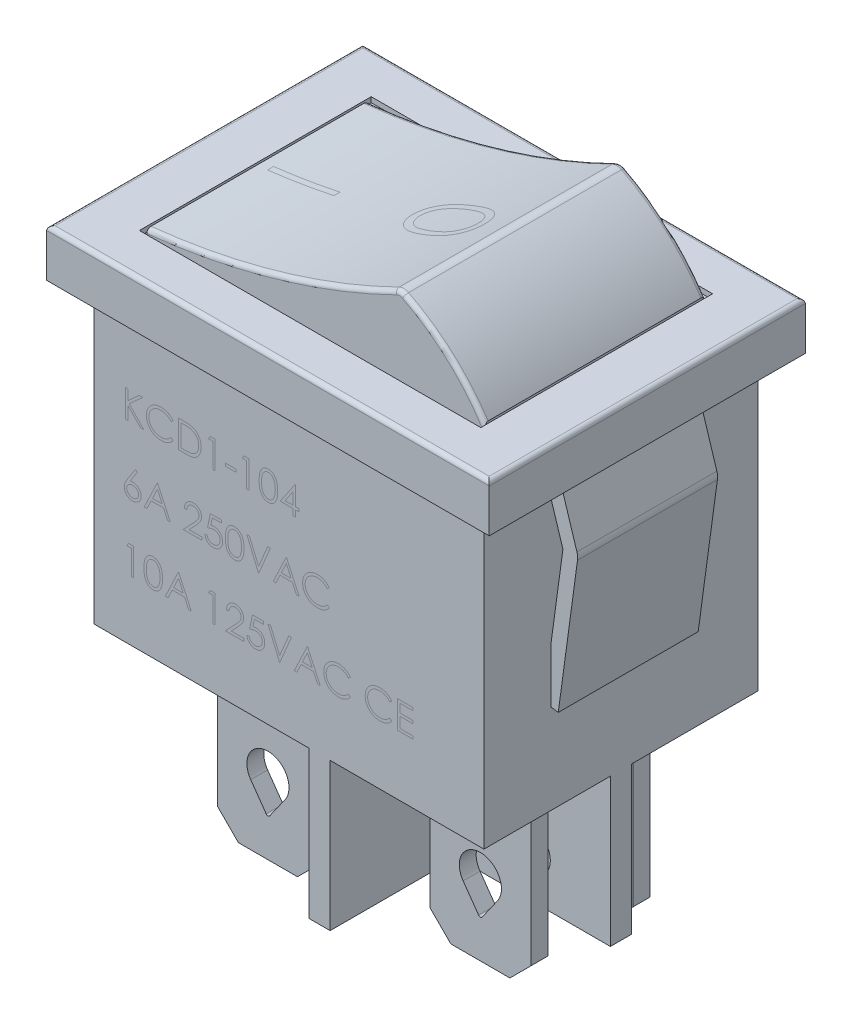
SolidWorks part; units mm, degrees
ref_plane "Front Plane" through (0, 0, 0) normal (0, 0, 1) x (1, 0, 0)
ref_plane "Top Plane" through (0, 0, 0) normal (0, 1, 0) x (1, 0, 0)
ref_plane "Right Plane" through (0, 0, 0) normal (1, 0, 0) x (0, 0, -1)
sketch "Sketch1" plane through (0, 0, 0) normal (0, 0, 1) x (1, 0, 0)
  line L1 (9.25, 7) -> (-9.25, 7)
  line L2 (9.25, 7) -> (9.25, -7)
  line L3 (9.25, -7) -> (-9.25, -7)
  line L4 (-9.25, 7) -> (-9.25, -7)
  line L5 (9.25, 7) -> (-9.25, -7) construction
  line L6 (9.25, -7) -> (-9.25, 7) construction
  point P0 (0, 0)
  dimension "D1" = 14
  dimension "D2" = 18.5
extrude "Boss-Extrude1" add sketch "Sketch1" along normal mid plane 13
sketch "Sketch2" plane through (0, 7, 0) normal (0, 1, 0) x (1, 0, 0)
  line L1 (10.5, 7.5) -> (-10.5, 7.5)
  line L2 (10.5, 7.5) -> (10.5, -7.5)
  line L3 (10.5, -7.5) -> (-10.5, -7.5)
  line L4 (-10.5, 7.5) -> (-10.5, -7.5)
  line L5 (10.5, 7.5) -> (-10.5, -7.5) construction
  line L6 (10.5, -7.5) -> (-10.5, 7.5) construction
  point P0 (0, 0)
  dimension "D1" = 15
  dimension "D2" = 21
extrude "Boss-Extrude2" add sketch "Sketch2" along normal blind 2.25
sketch "Sketch11" plane through (0, 9.25, 0) normal (0, 1, 0) x (1, 0, 0)
  line L1 (-8.1, -5.5) -> (8.1, -5.5)
  line L2 (-8.1, -5.5) -> (-8.1, 5.5)
  line L3 (-8.1, 5.5) -> (8.1, 5.5)
  line L4 (8.1, -5.5) -> (8.1, 5.5)
  line L5 (-8.1, -5.5) -> (8.1, 5.5) construction
  line L6 (-8.1, 5.5) -> (8.1, -5.5) construction
  line L7 (-10.5, 7.5) -> (-10.5, -7.5) construction
  point P0 (0, 0)
  dimension "D1" = 2.4
  dimension "D2" = 11
extrude "Cut-Extrude6" cut sketch "Sketch11" against normal blind 0.25
sketch "Sketch3" plane through (0, 0, 0) normal (0, 0, 1) x (1, 0, 0)
  line L0 (8, 9.25) -> (4, 12.75) construction
  line L1 (-8, 9.25) -> (-8.1, 9.25) construction
  line L2 (10.5, 9.25) -> (10.5, 7) construction
  line L4 (-10.5, 9.25) -> (-10.5, 7) construction
  line L5 (-8, 9.25) -> (8, 9.25) construction
  line L6 (-8, 9.25) -> (8, 9.25) construction
  line L7 (-8, 9.25) -> (-8, 8.95)
  line L8 (-8, 8.95) -> (8, 8.95)
  line L9 (8, 9.25) -> (8, 8.95)
  arc A0 (-8, 9.25) -> (3.779, 12.6405) centre (-11.6425, 44.0599) ccw
  arc A1 (4.2281, 12.6363) -> (8, 9.25) centre (-0.3483, 3.7449) cw
  arc A2 (3.779, 12.6405) -> (4.2281, 12.6363) centre (3.9993, 12.1917) cw
  point P6 (-8, 9.25)
  dimension "D4" = 35
  dimension "D5" = 6.5
  dimension "D6" = 10
  dimension "D7" = 0.5
  dimension "D1" = 2.5
  dimension "D2" = 3.5
  dimension "D3" = 2.5
  dimension "D8" = 0.3
extrude "Boss-Extrude3" add sketch "Sketch3" along normal mid plane 10.5
sketch "Sketch4" plane through (0, -7, 0) normal (0, -1, 0) x (-1, 0, 0)
  line L0 (-9.25, 6.5) -> (9.25, 6.5) construction
  line L1 (-1.95, 6.5) -> (-0.95, 6.5)
  line L2 (-1.95, 6.5) -> (-1.95, -6.5)
  line L3 (-1.95, -6.5) -> (-0.95, -6.5)
  line L4 (-0.95, 6.5) -> (-0.95, -6.5)
  line L5 (9.25, -6.5) -> (-9.25, -6.5) construction
  line L6 (-9.25, -6.5) -> (-9.25, 6.5) construction
  line L7 (-1.45, -6.5) -> (-1.45, 6.5) construction
  line L8 (-9.25, 0.5) -> (9.25, 0.5)
  line L9 (-9.25, 0.5) -> (-9.25, -0.5)
  line L10 (-9.25, -0.5) -> (9.25, -0.5)
  line L11 (9.25, 0.5) -> (9.25, -0.5)
  line L12 (-9.25, 0.5) -> (9.25, -0.5) construction
  line L13 (-9.25, -0.5) -> (9.25, 0.5) construction
  line L14 (9.25, -6.5) -> (9.25, 6.5) construction
  line L15 (0, 0) -> (4.2269, 0) construction
  line M5 (9.25, 6.5) -> (-9.25, 6.5)
  line M6 (-9.25, 6.5) -> (-9.25, -6.5)
  line M7 (-9.25, -6.5) -> (9.25, -6.5)
  line M8 (9.25, -6.5) -> (9.25, 6.5)
  dimension "D1" = 8.3
  dimension "D2" = 1
extrude "Boss-Extrude4" add sketch "Sketch4" along normal blind 7 contours L10 L2 L8 M6 | L4 L10 L8 M8 | L2 L10 L4 L8 | L2 L8 L4 M5 | L10 L2 L4 M7 region at (1.45, -7, -3.5) region at (1.45, -7, 0) region at (5.6, -7, 0) region at (-4.15, -7, 0) region at (1.45, -7, 3.5)
sketch "Sketch5" plane through (0, -7, 0) normal (0, -1, 0) x (1, 0, 0)
  line L0 (1.95, 6.5) -> (9.25, 6.5) construction
  line L1 (3, 2.82) -> (7.8, 2.82)
  line L2 (3, 2.82) -> (3, 2.02)
  line L3 (3, 2.02) -> (7.8, 2.02)
  line L4 (7.8, 2.82) -> (7.8, 2.02)
  line L5 (3, 2.82) -> (7.8, 2.02) construction
  line L6 (3, 2.02) -> (7.8, 2.82) construction
  line L7 (-6.2, -2.9) -> (-1.4, -2.9)
  line L8 (-6.2, -2.9) -> (-6.2, -3.7)
  line L9 (-6.2, -3.7) -> (-1.4, -3.7)
  line L10 (-1.4, -2.9) -> (-1.4, -3.7)
  line L11 (-6.2, -2.9) -> (-1.4, -3.7) construction
  line L12 (-6.2, -3.7) -> (-1.4, -2.9) construction
  line L13 (-9.25, -6.5) -> (0.95, -6.5) construction
  line L14 (9.25, 6.5) -> (9.25, -6.5) construction
  line L15 (0, 0) -> (-13.591, 0) construction
  line L16 (0, 0) -> (0, 9.8331) construction
  line L17 (3, -2.02) -> (7.8, -2.82) construction
  line L18 (3, -2.82) -> (7.8, -2.02) construction
  line L19 (7.8, -2.82) -> (7.8, -2.02)
  line L20 (3, -2.02) -> (7.8, -2.02)
  line L21 (3, -2.82) -> (3, -2.02)
  line L22 (3, -2.82) -> (7.8, -2.82)
  line L23 (-6.2, 3.7) -> (-1.4, 2.9) construction
  line L24 (-6.2, 2.9) -> (-1.4, 3.7) construction
  line L25 (-1.4, 2.9) -> (-1.4, 3.7)
  line L26 (-6.2, 3.7) -> (-1.4, 3.7)
  line L27 (-6.2, 2.9) -> (-6.2, 3.7)
  line L28 (-6.2, 2.9) -> (-1.4, 2.9)
  point P0 (5.4, 2.42)
  point P5 (-3.8, -3.3)
  point P24 (5.4, -2.42)
  point P29 (-3.8, 3.3)
  dimension "D1" = 4.8
  dimension "D2" = 0.8
  dimension "D3" = 14
  dimension "D4" = 3.68
  dimension "D5" = 2.8
  dimension "D6" = 1.45
extrude "Boss-Extrude5" add sketch "Sketch5" along normal blind 8.36
chamfer "Chamfer2" distance 1 angle 45 8 edges at (7.8, -15.36, 2.42) (3, -15.36, 2.42) (-1.4, -15.36, -3.3) (-6.2, -15.36, -3.3) (7.8, -15.36, -2.42) (3, -15.36, -2.42) (-1.4, -15.36, 3.3) (-6.2, -15.36, 3.3)
sketch "Sketch6" plane through (0, 0, 2.82) normal (0, 0, 1) x (1, 0, 0)
  line L0 (6.8, -15.36) -> (4, -15.36) construction
  line L1 (5.3183, -13.5177) -> (4.5832, -12.4769)
  line L2 (5.4, -11.9) -> (5.4, -15.36) construction
  line L3 (-1.4, -10.68) -> (3, -10.68) construction
  line L4 (5.4817, -13.5177) -> (6.2168, -12.4769)
  line L5 (-1.4, -14.36) -> (-1.4, -7) construction
  line L6 (3, -14.36) -> (3, -7) construction
  line L7 (0.8, -10.68) -> (0.8, -14.52) construction
  line L9 (-3.8817, -13.5177) -> (-4.6168, -12.4769)
  line L10 (-3.7183, -13.5177) -> (-2.9832, -12.4769)
  arc A0 (6.2168, -12.4769) -> (4.5832, -12.4769) centre (5.4, -11.9) ccw
  arc A1 (5.4817, -13.5177) -> (5.3183, -13.5177) centre (5.4, -13.46) cw
  arc A2 (-3.8817, -13.5177) -> (-3.7183, -13.5177) centre (-3.8, -13.46) ccw
  arc A3 (-4.6168, -12.4769) -> (-2.9832, -12.4769) centre (-3.8, -11.9) cw
  dimension "D1" = 0.1
  dimension "D2" = 2.66
  dimension "D3" = 1
  dimension "D4" = 1.8
extrude "Cut-Extrude1" cut sketch "Sketch6" against normal through all and the other way through all
ref_plane "Plane2" through (-3.071, 10.6688, 0) normal (0.2766, -0.961, 0) x (-0.961, -0.2766, 0)
sketch "Sketch7" plane through (-3.071, 10.6688, 0) normal (0.2766, -0.961, 0) x (-0.961, -0.2766, 0)
  text T0 "<r90>I</r>" font "Century Gothic" height 3.2
  text T1 "<r90>0</r>"
wrap "Wrap1" sketch "Sketch7" wrap type scribe source sketch "Sketch7" face at (-2.0357, 10.6854, 0)
sketch "Sketch8" plane through (0, 0, 6.5) normal (0, 0, 1) x (1, 0, 0)
  text T0 "KCD1-104\r\n6A 250VAC\r\n10A 125VAC CE" font "Century Gothic" height 1.3
wrap "Wrap2" sketch "Sketch8" wrap type scribe source sketch "Sketch8" face at (-0.3688, -6.125, 6.5)
sketch "Sketch9" plane through (0, 0, 0) normal (0, 0, 1) x (1, 0, 0)
  line L0 (-9.25, 7) -> (-10.175, 4.05)
  line L1 (-10.175, 4.05) -> (-9.25, -2.75)
  line L2 (-9.25, 7) -> (-9.25, -7) construction
  line L3 (9.25, 7) -> (10.175, 4.05)
  line L4 (10.175, 4.05) -> (9.25, -2.75)
  line L5 (9.25, -7) -> (9.25, 7) construction
  line L6 (-10.5, 7) -> (10.5, 7) construction
  dimension "D1" = 2.95
  dimension "D2" = 6.8
  dimension "D3" = 20.35
extrude "Extrude-Thin14" add sketch "Sketch9" against normal mid plane 6.64 separate body thin thin type mid plane wall 0.7
sketch "Sketch10" plane through (0, 0, 3.32) normal (0, 0, 1) x (1, 0, 0)
  line L2 (-9.25, -7) -> (9.25, -7)
  line L3 (-9.25, -7) -> (-9.25, 7)
  line L4 (-9.25, 7) -> (9.25, 7)
  line L5 (9.25, -7) -> (9.25, 7)
extrude "Cut-Extrude5" cut sketch "Sketch10" against normal through all
ref_axis "Ось1" through (0, -20.2999, 0) along (0, 1, 0)
fillet "Скругление1" radius 0.2 4 edges at (10.5, 9.25, 0) (0, 9.25, 7.5) (-10.5, 9.25, 0) (0, 9.25, -7.5)
fillet "Скругление2" radius 0.2 6 edges at (6.3322, 11.1861, -5.25) (4.004, 12.6917, -5.25) (6.3322, 11.1861, 5.25) (4.004, 12.6917, 5.25) (-1.9609, 10.4256, -5.25) (-1.9609, 10.4256, 5.25)
